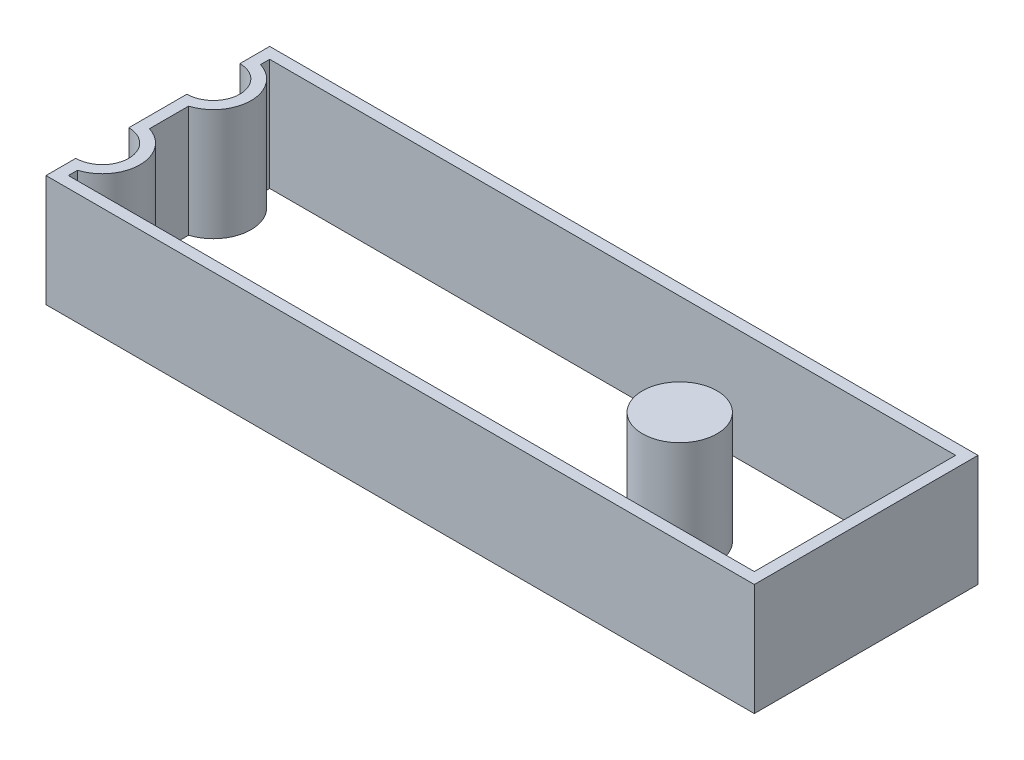
SolidWorks part; units mm, degrees
material "3.1355 (EN-AW 2024)"
ref_plane "Front" through (0, 0, 0) normal (0, 0, 1) x (1, 0, 0)
ref_plane "Top" through (0, 0, 0) normal (0, 1, 0) x (1, 0, 0)
ref_plane "Right" through (0, 0, 0) normal (1, 0, 0) x (0, 0, -1)
sketch "Эскиз1" plane through (0, 0, 0) normal (0, 1, 0) x (1, 0, 0)
  line L0 (0, 0) -> (0, 60) construction
  line L1 (0, 60) -> (190, 60)
  line L2 (190, 60) -> (190, 0)
  line L3 (190, 0) -> (0, 0)
  line L4 (0, 30) -> (140, 30) construction
  line L5 (0, 60) -> (0, 52)
  line L6 (0, 37.8) -> (0, 22.2)
  line L7 (0, 8) -> (0, 0)
  line L8 (140, 30) -> (190, 30) construction
  circle A0 centre (0, 44.9) radius 7.1 construction
  circle A1 centre (0, 15.1) radius 7.1 construction
  arc A2 (0, 52) -> (0, 37.8) centre (0, 44.9) cw
  arc A3 (0, 8) -> (0, 22.2) centre (0, 15.1) ccw
  point P11 (0, 52)
  point P12 (0, 37.8)
  dimension "D2" = 14.2
  dimension "D4" = 29.8
  dimension "D1" = 60
  dimension "D3" = 15.1
  dimension "D5" = 140
  dimension "D6" = 50
  dimension "D7" = 190
extrude "Бобышка-Вытянуть1" add sketch "Эскиз1" along normal blind 30
sketch "Эскиз2" plane through (0, 30, 0) normal (0, 1, 0) x (1, 0, 0)
  line L12 (3, 5.4558) -> (3, 3)
  line L13 (3, 3) -> (187, 3)
  line L14 (187, 3) -> (187, 57)
  line L15 (187, 57) -> (3, 57)
  line L16 (3, 57) -> (3, 54.5442)
  line L17 (3, 35.2558) -> (3, 24.7442)
  line L18 (3, 5.4558) -> (3, 3)
  line L19 (3, 3) -> (187, 3)
  line L20 (187, 3) -> (187, 57)
  line L21 (187, 57) -> (3, 57)
  line L22 (3, 57) -> (3, 54.5442)
  line L23 (3, 35.2558) -> (3, 24.7442)
  arc A4 (3, 35.2558) -> (3, 54.5442) centre (0, 44.9) ccw
  arc A5 (3, 5.4558) -> (3, 24.7442) centre (0, 15.1) ccw
  arc A6 (3, 35.2558) -> (3, 54.5442) centre (0, 44.9) ccw
  arc A7 (3, 5.4558) -> (3, 24.7442) centre (0, 15.1) ccw
  dimension "D1" = 3
extrude "Вырез-Вытянуть1" cut sketch "Эскиз2" against normal through all
sketch "Temp" plane through (0, 30, 0) normal (0, 1, 0) x (1, 0, 0)
  circle A0 centre (140, 30) radius 10
  dimension "D1" = 20
extrude "Бобышка-Вытянуть2" add sketch "Temp" against normal up to surface (30 mm away) separate body up to face at (50.775, 0, -30)
equation "\"D3@Эскиз1\"=8+\"D2@Эскиз1\"/2"
